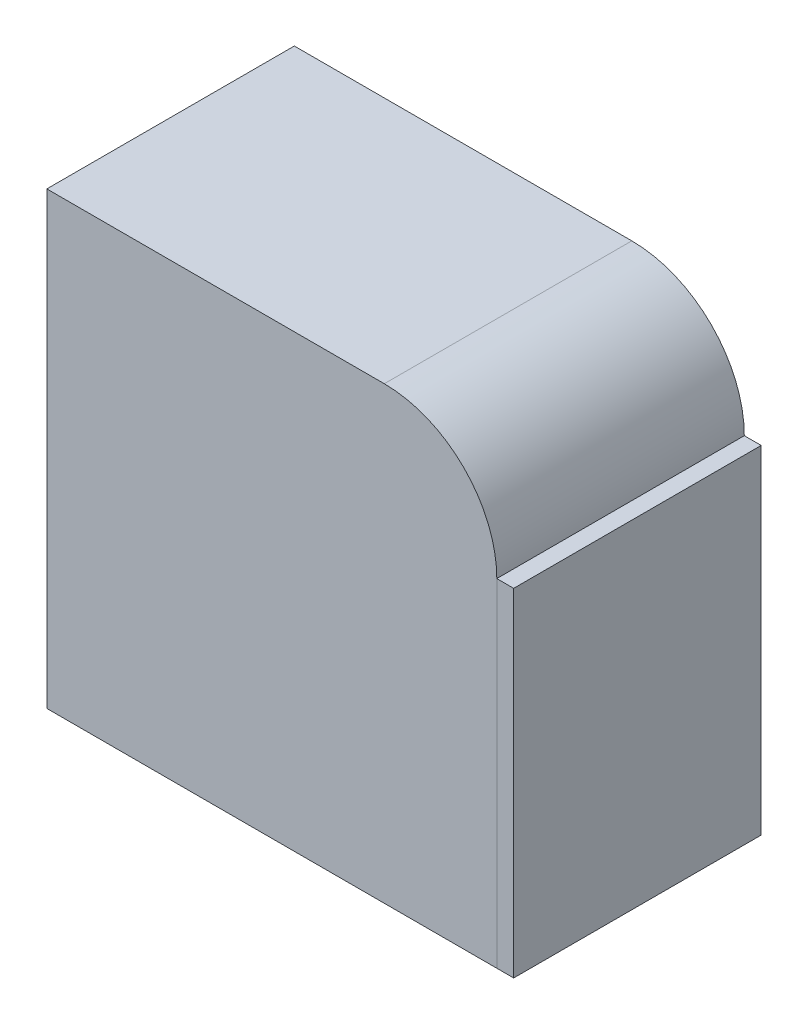
SolidWorks part; units mm, degrees
material "Pin"
ref_plane "Plan de face" through (0, 0, 0) normal (0, 0, 1) x (1, 0, 0)
ref_plane "Plan de dessus" through (0, 0, 0) normal (0, 1, 0) x (1, 0, 0)
ref_plane "Plan de droite" through (0, 0, 0) normal (1, 0, 0) x (0, 0, -1)
ref_axis "Axe1" through (0, 0, -18.9316) along (0, 0, 1)
sketch "Esquisse1" plane through (0, 0, 0) normal (0, 0, 1) x (1, 0, 0)
  line L5 (-58, -15) -> (-28, -15)
  line L6 (-58, -15) -> (-58, -55)
  line L7 (-58, -55) -> (-18, -55)
  line L8 (-18, -25) -> (-18, -55)
  arc A0 (-28, -15) -> (-18, -25) centre (-28, -25) cw
  dimension "D1" = 10
  dimension "D2" = 40
  dimension "D3" = 15
  dimension "D4" = 18
  dimension "D5" = 40
extrude "Boss.-Extru.1" add sketch "Esquisse1" along normal mid plane 22
sketch "Esquisse2" plane through (-18, 0, 0) normal (1, 0, 0) x (0, 0, -1)
  line L4 (11, -55) -> (11, -25)
  line L5 (11, -25) -> (-11, -25)
  line L6 (-11, -25) -> (-11, -55)
  line L7 (-11, -55) -> (11, -55)
  line L8 (11, -55) -> (11, -25)
  line L9 (11, -25) -> (-11, -25)
  line L10 (-11, -25) -> (-11, -55)
  line L11 (-11, -55) -> (11, -55)
  dimension "D1" = 0
extrude "Boss.-Extru.2" add sketch "Esquisse2" along normal blind 1.5 separate body
